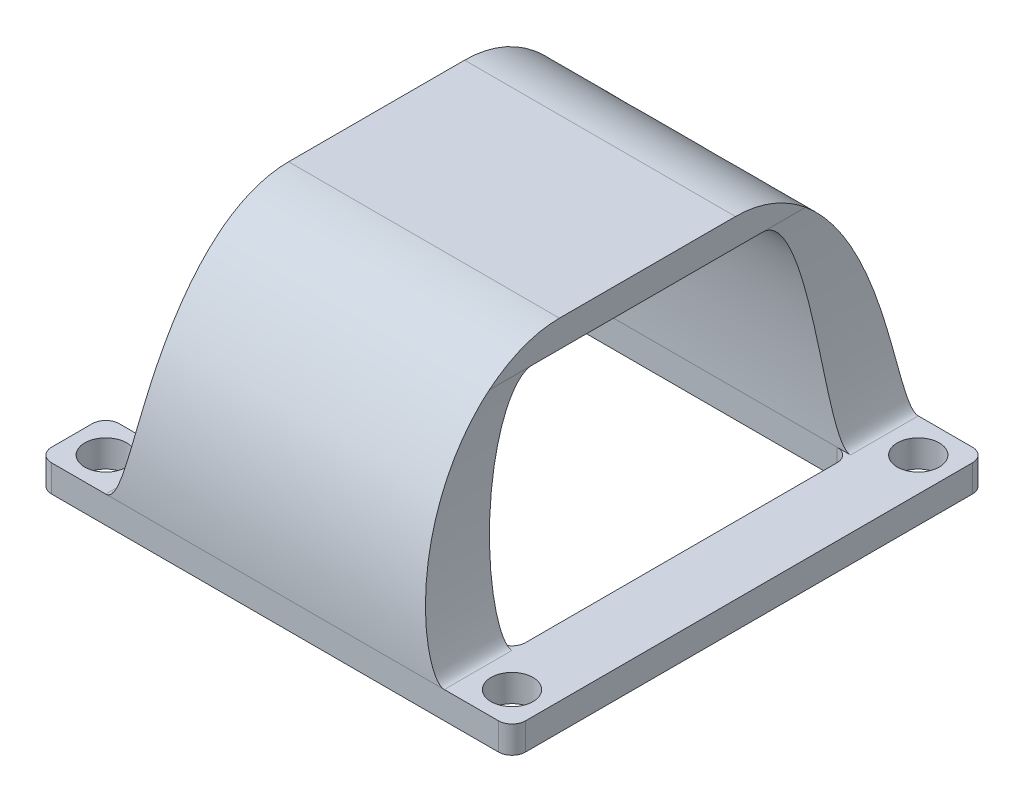
SolidWorks part; units mm, degrees
ref_plane "Plan de face" through (0, 0, 0) normal (0, 0, 1) x (1, 0, 0)
ref_plane "Plan de dessus" through (0, 0, 0) normal (0, 1, 0) x (1, 0, 0)
ref_plane "Plan de droite" through (0, 0, 0) normal (1, 0, 0) x (0, 0, -1)
sketch "Esquisse1" plane through (0, 0, 0) normal (0, 1, 0) x (1, 0, 0)
  line L0 (-12.5, 6.5) -> (-12.5, 12.5)
  line L1 (-15, -15) -> (15, -15) construction
  line L2 (-15, -15) -> (-15, 15) construction
  line L3 (-15, 15) -> (15, 15) construction
  line L4 (15, -15) -> (15, 15) construction
  line L5 (-15, -15) -> (15, 15) construction
  line L6 (-15, 15) -> (15, -15) construction
  line L7 (-17.5, -17.5) -> (17.5, -17.5)
  line L9 (-17.5, 17.5) -> (17.5, 17.5)
  line L10 (17.5, -17.5) -> (17.5, 17.5)
  line L11 (-17.5, -17.5) -> (17.5, 17.5) construction
  line L12 (-17.5, 17.5) -> (17.5, -17.5) construction
  line L13 (-12.5, 12.5) -> (12.5, 12.5)
  line L14 (12.5, 12.5) -> (12.5, -12.5)
  line L15 (12.5, -12.5) -> (-12.5, -12.5)
  line L16 (-12.5, -12.5) -> (-17.5, -12.5)
  line L17 (-17.5, 17.5) -> (-17.5, 6.5)
  line L18 (-17.5, -12.5) -> (-17.5, -17.5)
  circle A0 centre (15, 15) radius 1.55
  circle A1 centre (15, -15) radius 1.55
  circle A2 centre (-15, -15) radius 1.55
  circle A3 centre (-15, 6.5) radius 1.55
  arc A4 (-17.5, 6.5) -> (-12.5, 6.5) centre (-15, 6.5) ccw
  point P0 (0, 0)
  point P11 (0, 0)
  dimension "D1" = 30
  dimension "D2" = 8.5
  dimension "D3" = 3.1
  dimension "D4" = 35
extrude "Boss.-Extru.1" add sketch "Esquisse1" along normal blind 2
ref_plane "Plan1" through (0, 17, 0) normal (0, 1, 0) x (1, 0, 0)
sketch "Esquisse2" plane through (0, 17, 0) normal (0, 1, 0) x (1, 0, 0)
  line L0 (17.5, 17.5) -> (-17.5, 17.5) construction
  line L1 (-10, -17.5) -> (10, -17.5)
  line L2 (-10, -17.5) -> (-10, 17.5)
  line L3 (-10, 17.5) -> (10, 17.5)
  line L4 (10, -17.5) -> (10, 17.5)
  line L5 (-10, -17.5) -> (10, 17.5) construction
  line L6 (-10, 17.5) -> (10, -17.5) construction
  point P1 (0, 0)
  dimension "D1" = 20
extrude "Boss.-Extru.2" add sketch "Esquisse2" along normal blind 2 separate body
sketch "Esquisse3" plane through (0, 2, 0) normal (0, 1, 0) x (1, 0, 0)
  line L0 (0, 0) -> (0, 17.5) construction
  line L1 (17.5, 17.5) -> (-17.5, 17.5) construction
  line L2 (0, 0) -> (0, -17.5) construction
  line L3 (-17.5, -17.5) -> (17.5, -17.5) construction
  line L4 (-12.5, 12.5) -> (12.5, 12.5) construction
  line L5 (-10.45, 0) -> (10.45, 0) construction
  line L6 (-10, 12.5) -> (10, 12.5)
  line L7 (-10, 12.5) -> (-10, 17.5)
  line L8 (-10, 17.5) -> (10, 17.5)
  line L9 (10, 12.5) -> (10, 17.5)
  line L10 (-10, 12.5) -> (10, 17.5) construction
  line L11 (-10, 17.5) -> (10, 12.5) construction
  line L12 (-10, -17.5) -> (10, -12.5) construction
  line L13 (-10, -12.5) -> (10, -17.5) construction
  line L14 (10, -12.5) -> (10, -17.5)
  line L15 (-10, -17.5) -> (10, -17.5)
  line L16 (-10, -12.5) -> (-10, -17.5)
  line L17 (-10, -12.5) -> (10, -12.5)
  point P5 (0, 15)
  point P9 (0, 15)
  point P12 (0, 12.5)
  point P23 (0, -12.5)
  point P24 (0, -15)
  dimension "D1" = 2.5
  dimension "D2" = 20
extrude "Boss.-Extru.3" add sketch "Esquisse3" along normal up to next
fillet "Congé1" radius 4 2 edges at (0, 17, 12.5) (0, 17, -12.5)
fillet "Congé2" radius 17 2 edges at (0, 19, 17.5) (0, 19, -17.5)
fillet "Congé3" radius 2.5 4 edges
fillet "Congé4" radius 1 8 edges at (-17.5, 1, -17.5) (17.5, 1, -17.5) (17.5, 1, 17.5) (-17.5, 1, 17.5) (-17.5, 1, 12.5)
